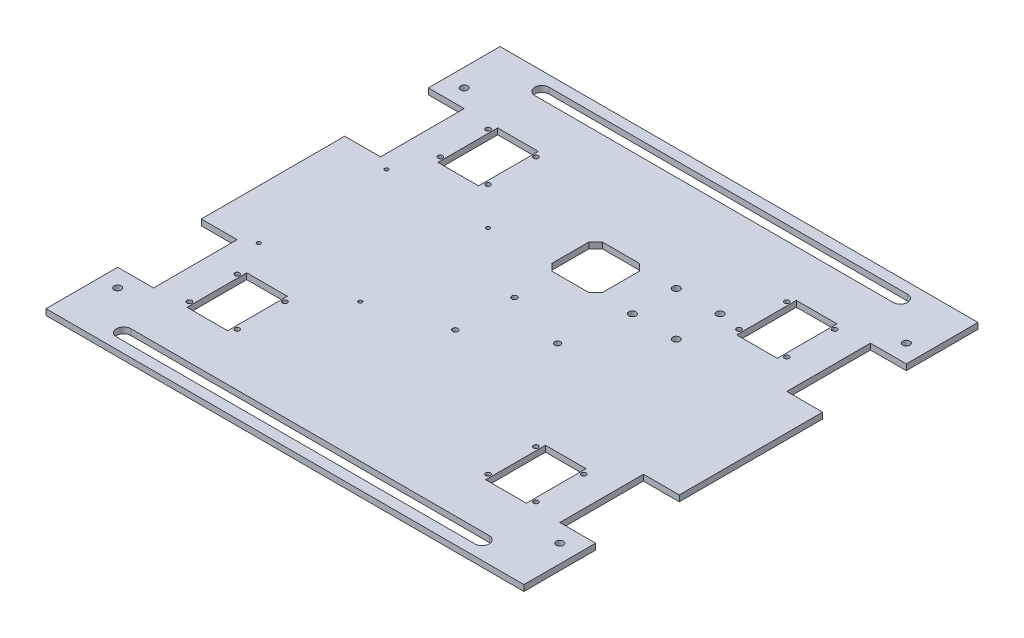
SolidWorks part; units mm, degrees
ref_plane "前基準面" through (0, 0, 0) normal (0, 0, 1) x (1, 0, 0)
ref_plane "上基準面" through (0, 0, 0) normal (0, 1, 0) x (1, 0, 0)
ref_plane "右基準面" through (0, 0, 0) normal (1, 0, 0) x (0, 0, -1)
sketch "草圖1" plane through (0, 0, 0) normal (0, 1, 0) x (1, 0, 0)
  line L0 (200, 190) -> (200, -190)
  line L1 (200, 190) -> (-200, 190)
  line L3 (200, -190) -> (-200, -190)
  line L4 (-200, 190) -> (-200, -190)
  line L5 (0, -190) -> (0, 190) construction
  line L6 (200, 0) -> (-200, 0) construction
  line L8 (-200, 130) -> (-200, -130) construction
  line L10 (-170, 130) -> (-170, -130) construction
  line L11 (-200, 130) -> (200, 130) construction
  line L12 (-200, 130) -> (-200, 190) construction
  line L13 (-200, 190) -> (200, 190) construction
  line L15 (-200, -130) -> (200, -130) construction
  line L16 (-200, -130) -> (-200, -190) construction
  line L17 (-200, -190) -> (200, -190) construction
  line L19 (170, 130) -> (170, -130) construction
  point P0 (0, 0)
  dimension "D1" = 400
  dimension "D2" = 260
  dimension "D3" = 60
  dimension "D4" = 60
  dimension "D5" = 30
extrude "填料-伸長1" add sketch "草圖1" along normal blind 5
sketch "草圖2" plane through (0, 5, 0) normal (0, 1, 0) x (1, 0, 0)
  line L0 (200, -190) -> (200, 190) construction
  line L1 (-200, 190) -> (200, 190) construction
  line L5 (-185, 190) -> (-185, -190) construction
  line L21 (-200, 190) -> (200, 190) construction
  line L22 (-200, 190) -> (-200, 130) construction
  line L23 (-200, 130) -> (200, 130) construction
  line L24 (-275.3304, 0) -> (275.3304, 0) construction
  line L25 (0, 247.3454) -> (0, -229.8147) construction
  line L42 (200, 190) -> (200, 130) construction
  line L44 (-41.25, 25) -> (41.25, 25) construction
  line L45 (-41.25, 25) -> (-41.25, -45) construction
  line L46 (-41.25, -45) -> (41.25, -45) construction
  line L47 (41.25, 25) -> (41.25, -45) construction
  line L59 (-200, 160) -> (200, 160) construction
  line L60 (-200, 145) -> (200, 145) construction
  line L61 (-200, -145) -> (200, -145) construction
  line L62 (-200, -160) -> (200, -160) construction
  line L63 (-200, -130) -> (200, -130) construction
  line L64 (200, -190) -> (200, -130) construction
  line L65 (-200, -190) -> (200, -190) construction
  line L66 (-200, -190) -> (-200, -130) construction
  line L67 (185, -190) -> (185, 190) construction
  line L68 (-200, 130) -> (-170, 130) construction
  line L69 (-200, 130) -> (-200, -130) construction
  line L70 (-200, -130) -> (-170, -130) construction
  line L71 (-170, 130) -> (-170, -130) construction
  line L72 (200, 130) -> (170, 130) construction
  line L73 (200, 130) -> (200, -130) construction
  line L74 (200, -130) -> (170, -130) construction
  line L75 (170, 130) -> (170, -130) construction
  line L76 (170, -60) -> (200, -60)
  line L77 (-200, 130) -> (-170, 130)
  line L78 (-200, 130) -> (-200, 60)
  line L79 (-200, 60) -> (-170, 60)
  line L80 (-170, 130) -> (-170, 60)
  line L81 (-170, -130) -> (-200, -130)
  line L82 (-170, -130) -> (-170, -60)
  line L83 (-170, -60) -> (-200, -60)
  line L84 (-200, -130) -> (-200, -60)
  line L85 (200, -130) -> (200, -60)
  line L86 (170, -130) -> (200, -130)
  line L87 (170, -130) -> (170, -60)
  line L88 (200, 60) -> (170, 60)
  line L89 (170, 130) -> (170, 60)
  line L90 (200, 130) -> (170, 130)
  line L91 (200, 130) -> (200, 60)
  line L100 (100, -80) -> (150, -80) construction
  line L101 (46.15, 91.35) -> (88.85, 91.35) construction
  line L102 (46.15, 91.35) -> (46.15, 48.65) construction
  line L103 (46.15, 48.65) -> (88.85, 48.65) construction
  line L104 (88.85, 91.35) -> (88.85, 48.65) construction
  line L105 (-150, -80) -> (-100, -80) construction
  line L106 (-150, -80) -> (-150, -130) construction
  line L107 (-150, -130) -> (-100, -130) construction
  line L108 (-100, -80) -> (-100, -130) construction
  line L109 (-142, -80) -> (-108, -80)
  line L110 (-142, -80) -> (-142, -130)
  line L111 (-142, -130) -> (-108, -130)
  line L112 (-108, -80) -> (-108, -130)
  line L113 (100, -80) -> (100, -130) construction
  line L114 (100, -130) -> (150, -130) construction
  line L115 (150, -80) -> (150, -130) construction
  line L116 (108, -80) -> (142, -80)
  line L117 (108, -80) -> (108, -130)
  line L118 (108, -130) -> (142, -130)
  line L119 (142, -80) -> (142, -130)
  line L120 (-150, 130) -> (-100, 130) construction
  line L121 (-150, 130) -> (-150, 80) construction
  line L122 (-150, 80) -> (-100, 80) construction
  line L123 (-100, 130) -> (-100, 80) construction
  line L124 (-142, 130) -> (-108, 130)
  line L125 (-142, 130) -> (-142, 80)
  line L126 (-142, 80) -> (-108, 80)
  line L127 (-108, 130) -> (-108, 80)
  line L128 (100, 130) -> (150, 130) construction
  line L129 (100, 130) -> (100, 80) construction
  line L130 (100, 80) -> (150, 80) construction
  line L131 (150, 130) -> (150, 80) construction
  line L132 (108, 130) -> (142, 130)
  line L133 (108, 130) -> (108, 80)
  line L134 (108, 80) -> (142, 80)
  line L135 (142, 130) -> (142, 80)
  line L136 (-21.15, 85.5) -> (-15.5, 91.15)
  line L137 (-72, -55) -> (-160, -55) construction
  line L138 (-72, -55) -> (-72, 55) construction
  line L139 (-72, 55) -> (-160, 55) construction
  line L140 (-160, -55) -> (-160, 55) construction
  line L141 (-15.5, 91.15) -> (15.5, 91.15)
  line L142 (-21.15, 85.5) -> (-21.15, 54.5)
  line L143 (-15.5, 48.85) -> (15.5, 48.85)
  line L144 (21.15, 85.5) -> (21.15, 54.5)
  line L145 (15.5, 91.15) -> (21.15, 85.5)
  line L146 (15.5, 48.85) -> (21.15, 54.5)
  line L147 (-21.15, 54.5) -> (-15.5, 48.85)
  line L148 (-234.8869, -145) -> (-234.8869, -175) construction
  line L149 (-214.8869, -145) -> (-214.8869, -175)
  line L150 (-254.8869, -145) -> (-254.8869, -175)
  line L151 (-234.8869, 145) -> (-234.8869, 175) construction
  line L152 (-214.8869, 145) -> (-214.8869, 175)
  line L153 (-254.8869, 145) -> (-254.8869, 175)
  line L154 (234.8869, -145) -> (234.8869, -175) construction
  line L155 (214.8869, -145) -> (214.8869, -175)
  line L156 (254.8869, -145) -> (254.8869, -175)
  line L157 (234.8869, 145) -> (234.8869, 175) construction
  line L158 (214.8869, 145) -> (214.8869, 175)
  line L159 (254.8869, 145) -> (254.8869, 175)
  line L160 (-150, 175) -> (150, 175) construction
  line L161 (-150, 181) -> (150, 181)
  line L162 (-150, 169) -> (150, 169)
  line L163 (-150, -175) -> (150, -175) construction
  line L164 (-150, -181) -> (150, -181)
  line L165 (-150, -169) -> (150, -169)
  circle A21 centre (-13.32, -34.13) radius 2.25
  circle A22 centre (-12.05, 14.13) radius 2.25
  circle A23 centre (39.25, -1.11) radius 2.5
  circle A32 centre (-185, 145) radius 3
  circle A33 centre (185, 145) radius 3
  circle A34 centre (-185, -145) radius 3
  circle A35 centre (185, -145) radius 3
  circle A40 centre (49.15, 88.35) radius 3
  circle A41 centre (85.85, 88.35) radius 3
  circle A42 centre (49.15, 51.65) radius 3
  circle A43 centre (85.85, 51.65) radius 3
  circle A44 centre (-145, -85) radius 2
  circle A45 centre (-105, -85) radius 2
  circle A46 centre (-145, -125) radius 2
  circle A47 centre (-105, -125) radius 2
  circle A48 centre (105, -85) radius 2
  circle A49 centre (145, -85) radius 2
  circle A50 centre (105, -125) radius 2
  circle A51 centre (145, -125) radius 2
  circle A52 centre (-145, 125) radius 2
  circle A53 centre (-105, 125) radius 2
  circle A54 centre (-145, 85) radius 2
  circle A55 centre (-105, 85) radius 2
  circle A56 centre (105, 125) radius 2
  circle A57 centre (145, 125) radius 2
  circle A58 centre (105, 85) radius 2
  circle A59 centre (145, 85) radius 2
  circle A60 centre (-158.45, 53.45) radius 1.55
  circle A61 centre (-73.55, 53.45) radius 1.55
  circle A62 centre (-158.45, -53.45) radius 1.55
  circle A63 centre (-73.55, -53.45) radius 1.55
  circle A64 centre (-15.5, 85.5) radius 1.5 construction
  circle A65 centre (15.5, 85.5) radius 1.5 construction
  circle A66 centre (-15.5, 54.5) radius 1.5 construction
  circle A67 centre (15.5, 54.5) radius 1.5 construction
  arc A68 (-214.8869, -145) -> (-254.8869, -145) centre (-234.8869, -145) ccw
  arc A69 (-254.8869, -175) -> (-214.8869, -175) centre (-234.8869, -175) ccw
  arc A70 (-214.8869, 145) -> (-254.8869, 145) centre (-234.8869, 145) cw
  arc A71 (-254.8869, 175) -> (-214.8869, 175) centre (-234.8869, 175) cw
  arc A72 (214.8869, -145) -> (254.8869, -145) centre (234.8869, -145) cw
  arc A73 (254.8869, -175) -> (214.8869, -175) centre (234.8869, -175) cw
  arc A74 (214.8869, 145) -> (254.8869, 145) centre (234.8869, 145) ccw
  arc A75 (254.8869, 175) -> (214.8869, 175) centre (234.8869, 175) ccw
  arc A76 (-150, 181) -> (-150, 169) centre (-150, 175) ccw
  arc A77 (150, 169) -> (150, 181) centre (150, 175) ccw
  arc A78 (-150, -181) -> (-150, -169) centre (-150, -175) cw
  arc A79 (150, -169) -> (150, -181) centre (150, -175) cw
  point P54 (0, 70)
  point P55 (0, 91.15)
  point P56 (-234.8869, -160)
  point P62 (0, -10)
  point P64 (-41.25, -10)
  point P70 (-234.8869, -125)
  point P71 (-234.8869, -195)
  point P73 (0, 175)
  point P89 (-234.8869, 160)
  point P102 (0, 25)
  point P175 (-116, 55)
  point P177 (-160, 0)
  point P182 (-116, 0)
  point P183 (67.5, 91.35)
  point P185 (46.15, 70)
  point P187 (234.8869, -160)
  point P191 (67.5, 70)
  point P195 (234.8869, 160)
  point P204 (-21.15, 91.15)
  point P205 (21.15, 48.85)
  point P206 (-21.15, 48.85)
  point P207 (21.15, 91.15)
  point P224 (-21.15, 70)
  point P227 (0, -175)
  dimension "D5" = 60
  dimension "D6" = 15
  dimension "D7" = 30
  dimension "D9" = 6
  dimension "D18" = 4.5
  dimension "D25" = 5
  dimension "D28" = 42.7
  dimension "D35" = 10
  dimension "D10" = 6
  dimension "D13" = 70
  dimension "D30" = 6
  dimension "D31" = 50
  dimension "D32" = 50
  dimension "D33" = 40
  dimension "D37" = 4
  dimension "D46" = 4
  dimension "D55" = 4
  dimension "D64" = 4
  dimension "D73" = 3.1
  dimension "D77" = 3
  dimension "D26" = 6
  dimension "D3" = 15
  dimension "D4" = 15
  dimension "D11" = 70
  dimension "D12" = 40
  dimension "D14" = 120
  dimension "D15" = 25
  dimension "D16" = 82.5
  dimension "D17" = 70
  dimension "D19" = 10.87
  dimension "D20" = 27.93
  dimension "D21" = 29.2
  dimension "D22" = 10.87
  dimension "D23" = 26.11
  dimension "D24" = 2
  dimension "D27" = 15
  dimension "D29" = 42.7
  dimension "D34" = 300
  dimension "D36" = 40
  dimension "D38" = 5
  dimension "D90" = 15
  dimension "D39" = 5
  dimension "D40" = 34
  dimension "D41" = 8
  dimension "D42" = 50
  dimension "D43" = 50
  dimension "D44" = 40
  dimension "D45" = 40
  dimension "D47" = 5
  dimension "D48" = 5
  dimension "D49" = 34
  dimension "D50" = 8
  dimension "D51" = 50
  dimension "D52" = 50
  dimension "D53" = 40
  dimension "D54" = 40
  dimension "D56" = 5
  dimension "D57" = 5
  dimension "D58" = 34
  dimension "D59" = 8
  dimension "D60" = 50
  dimension "D61" = 50
  dimension "D62" = 40
  dimension "D63" = 40
  dimension "D65" = 5
  dimension "D66" = 5
  dimension "D67" = 34
  dimension "D68" = 8
  dimension "D69" = 20
  dimension "D70" = 20
  dimension "D71" = 88
  dimension "D72" = 110
  dimension "D74" = 10
  dimension "D75" = 42.3
  dimension "D76" = 42.3
  dimension "D78" = 31
  dimension "D79" = 31
  dimension "D80" = 5.65
  dimension "D81" = 5.65
  dimension "D82" = 5.65
  dimension "D83" = 5.65
  dimension "D84" = 5.65
  dimension "D85" = 5.65
  dimension "D86" = 5.65
  dimension "D87" = 5.65
  dimension "D88" = 5.65
  dimension "D89" = 5.65
extrude "除料-伸長1" cut sketch "草圖2" against normal through all
